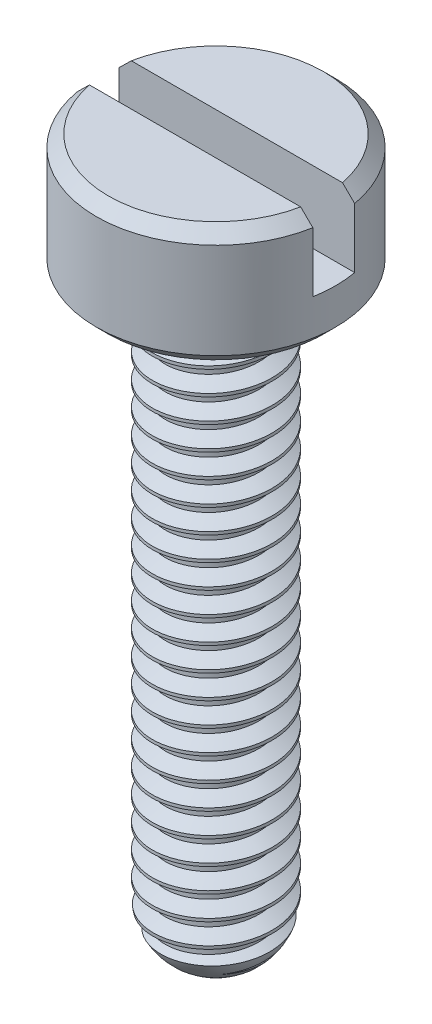
SolidWorks part; units mm, degrees
ref_plane "Front Plane" through (0, 0, 0) normal (0, 0, 1) x (1, 0, 0)
ref_plane "Top Plane" through (0, 0, 0) normal (0, 1, 0) x (1, 0, 0)
ref_plane "Right Plane" through (0, 0, 0) normal (1, 0, 0) x (0, 0, -1)
sketch "Sketch1" plane through (0, 0, 0) normal (0, 1, 0) x (1, 0, 0)
  circle A0 centre (0, 0) radius 2
  dimension "D1" = 4
extrude "Boss-Extrude1" add sketch "Sketch1" along normal blind 2
sketch "Sketch2" plane through (0, 0, 0) normal (0, -1, 0) x (1, 0, 0)
  circle A0 centre (0, 0) radius 1
  dimension "D1" = 2
extrude "Boss-Extrude2" add sketch "Sketch2" along normal blind 10
chamfer "Chamfer1" distance 0.2 angle 45 2 edges at (0, 0, 2) (0, 2, 2)
ref_plane "Plane2" through (0, -11, 0) normal (0, -1, 0) x (-1, 0, 0)
fillet "Fillet1" radius 1 1 edges at (0, -10, -1)
thread "Thread1" pitch 0.4 method cut profile "Thread Profile2" start angle 0, offset 0, length 0, pitch 0.4, diameter 2
ref_plane "Plane3" through (1, -11, 0) normal (0, 0, 1) x (1, 0, 0)
sketch "Thread Profile2" plane through (1, -11, 0) normal (0, 0, 1) x (1, 0, 0)
  line L0 (0, 0) -> (0, 0.4) construction
  line L11 (0, 0) -> (0, 0.35)
  line L12 (0, 0.35) -> (-0.2165, 0.225)
  line L13 (-0.2165, 0.225) -> (-0.2165, 0.125)
  line L15 (-0.2165, 0.125) -> (0, 0)
  line L17 (-0.2165, 0.175) -> (0, 0.175) construction
  point P2 (0, 0)
  dimension "Pitch" = 0.4
  dimension "Profile_Angle" = 60
  dimension "Profile_Land" = 0.1
  dimension "Profile_Height" = 0.2165
sketch "Sketch8" plane through (0, 0, 0) normal (1, 0, 0) x (0, 0, -1)
  line L0 (1.8, 2) -> (-1.8, 2) construction
  line L1 (-0.35, 2) -> (0.35, 2)
  line L2 (-0.35, 2) -> (-0.35, 0.8)
  line L3 (-0.35, 0.8) -> (0.35, 0.8)
  line L4 (0.35, 2) -> (0.35, 0.8)
  point P4 (0, 2)
  dimension "D1" = 1.2
  dimension "D2" = 0.7
extrude "Cut-Extrude1" cut sketch "Sketch8" against normal through all both and the other way through all
